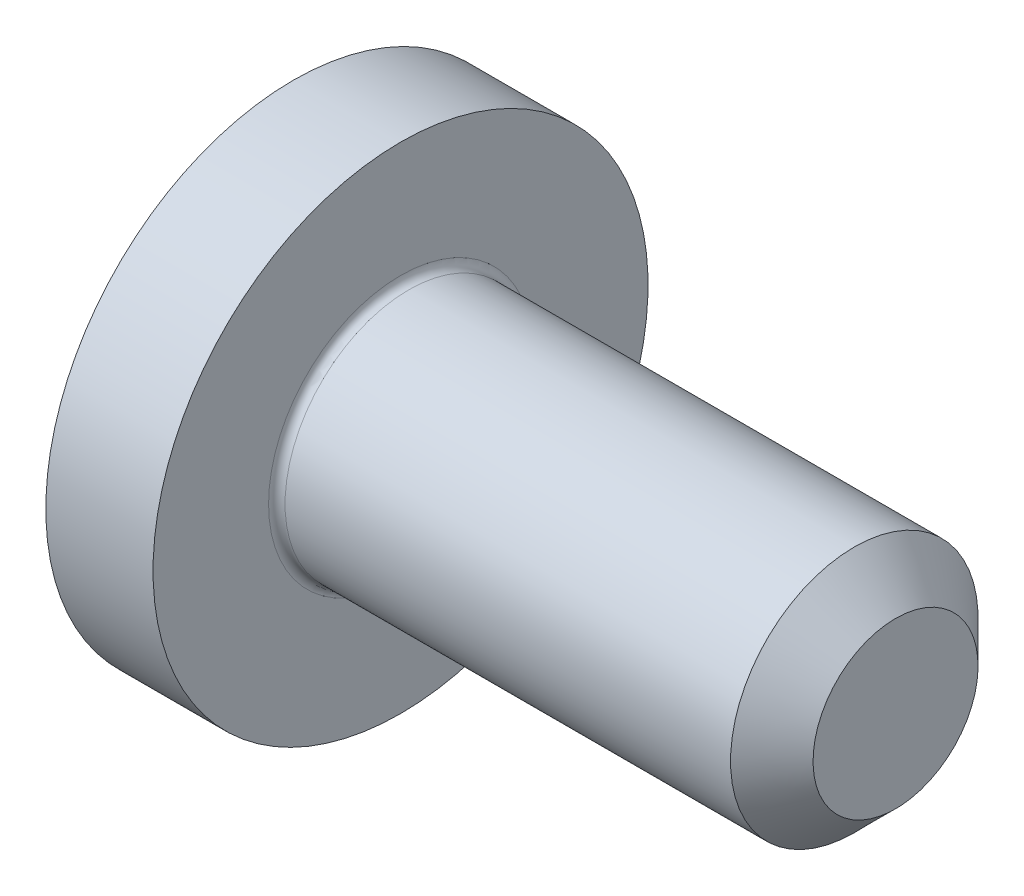
SolidWorks part; units mm, degrees
ref_plane "Front Plane" through (0, 0, 0) normal (0, 0, 1) x (1, 0, 0)
ref_plane "Top Plane" through (0, 0, 0) normal (0, 1, 0) x (1, 0, 0)
ref_plane "Right Plane" through (0, 0, 0) normal (1, 0, 0) x (0, 0, -1)
ref_axis "Axis_X" through (-88.99, 0, 0) along (1, 0, 0)
ref_axis "Axis_Y" through (0, 55, 0) along (0, -1, 0)
ref_axis "Axis_Z" through (0, 0, -88.99) along (0, 0, 1)
sketch "Sketch1" plane through (0, 0, 0) normal (0, 0, 1) x (1, 0, 0)
  line L0 (-1.3, 0) -> (6, 0)
  line L1 (6, 0) -> (6, -1)
  line L2 (6, -1) -> (5.5, -1.5)
  line L3 (5.5, -1.5) -> (0.1, -1.5)
  line L4 (0, -1.6) -> (0, -3)
  line L5 (0, -3) -> (-1.3, -3)
  line L7 (-1.3, -3) -> (-1.3, 0)
  line L8 (6, 0) -> (-1.3, 0) construction
  line L9 (6, 1) -> (5.5, 1.5) construction
  arc A0 (0.1, -1.5) -> (0, -1.6) centre (0.1, -1.6) ccw
  point P7 (-1.3, 3)
  point P11 (5.5, -1.5)
  point P12 (1.6, 0)
  dimension "R_s" = 0.1
  dimension "M" = 3
  dimension "L" = 6
  dimension "BLT_2" = 1.3
  dimension "A" = 6
  dimension "BLT_1" = 0.5
  dimension "Pitch" = 0.5
  dimension "D2" = 45
  dimension "E_s" = 1.6
revolve "Revolve1" add sketch "Sketch1" angle 360 about L8
sketch "Sketch2" plane through (-1.3, 0, 0) normal (-1, 0, 0) x (0, 0, 1)
  line L1 (0, 0.866) -> (-0.75, 0.433)
  line L2 (-0.75, 0.433) -> (-0.75, -0.433)
  line L3 (-0.75, -0.433) -> (0, -0.866)
  line L4 (0, -0.866) -> (0.75, -0.433)
  line L5 (0.75, -0.433) -> (0.75, 0.433)
  line L6 (0.75, 0.433) -> (0, 0.866)
  circle A0 centre (0, 0) radius 0.75 construction
  dimension "B" = 1.5
extrude "Cut-Extrude1" cut sketch "Sketch2" against normal blind 2
equation "\"Factor\"= 1.082532"
equation "\"Pitch\"= iif ( \"M\" = 12 , 1.75 , iif ( \"M\" = 10 , 1.5 , iif ( \"M\" = 8 , 1.25 , iif ( \"M\" = 6 , 1 , iif ( \"M\" = 5 , 0.8 , iif ( \"M\" = 4 , 0.7 , iif ( \"M\" = 3 , 0.5 , iif ( \"M\" = 2.6 or \"M\" = 2.5 , 0.45 , 0.4 ) ) ) ) ) ) ) )"
equation "\"ATD_1\"= round ( \"M\" - \"Factor\" * \"Pitch\" , 3 )"
equation "\"ATL_1\"= \"L\" - \"E_s@Sketch1\""
equation "\"Cut-Revolve1\"= iif ( \"L\" > 10 , \"unsuppressed\" , \"suppressed\" )"
equation "\"BLT_1\"= \"Pitch\""
